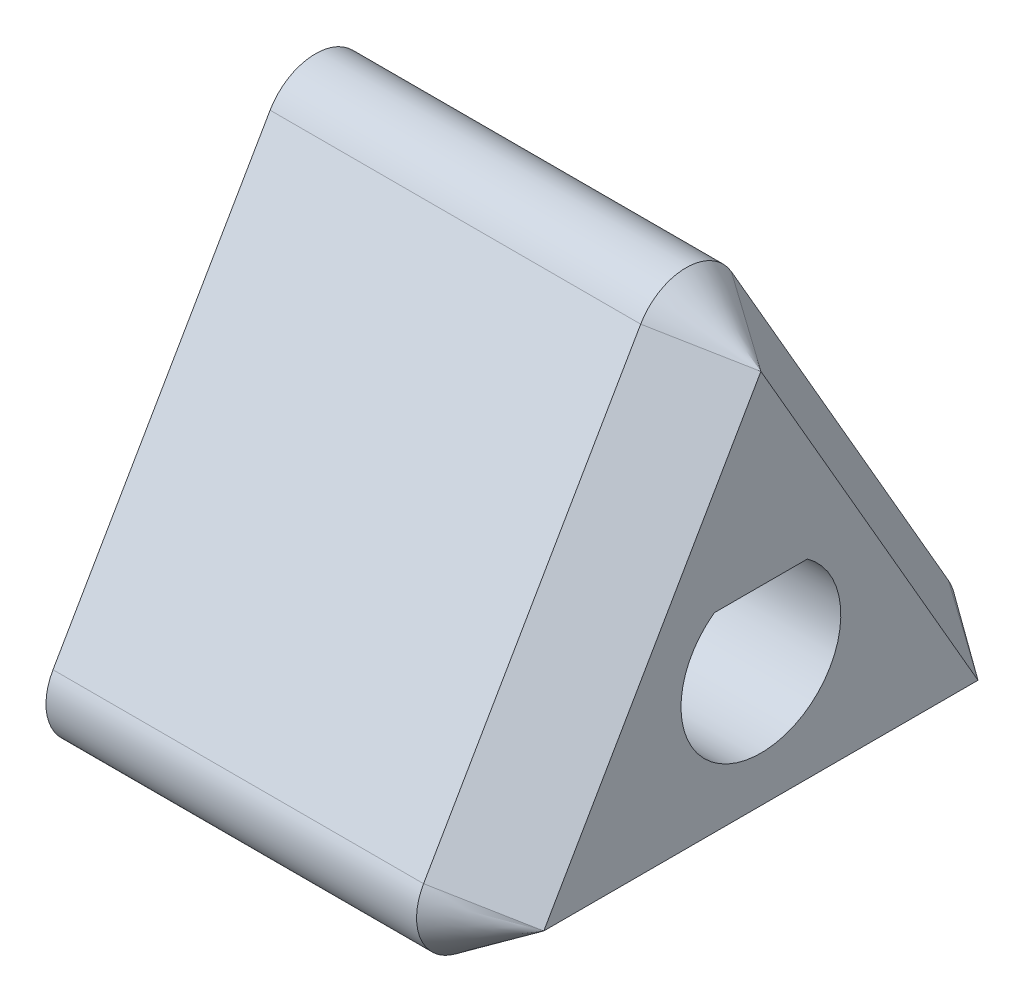
SolidWorks part; units mm, degrees
ref_plane "Ebene vorne" through (0, 0, 0) normal (0, 0, 1) x (1, 0, 0)
ref_plane "Ebene oben" through (0, 0, 0) normal (0, 1, 0) x (1, 0, 0)
ref_plane "Ebene rechts" through (0, 0, 0) normal (1, 0, 0) x (0, 0, -1)
sketch "Skizze1" plane through (0, 0, 0) normal (1, 0, 0) x (0, 0, -1)
  line L1 (0, 13.5677) -> (-11.75, -6.7839)
  line L2 (-11.75, -6.7839) -> (11.75, -6.7839)
  line L3 (11.75, -6.7839) -> (0, 13.5677)
  circle A0 centre (0, 0) radius 6.7839 construction
  dimension "D1" = 23.5
extrude "Aufsatz-Linear austragen1" add sketch "Skizze1" along normal blind 17
sketch "Skizze2" plane through (17, 0, 0) normal (1, 0, 0) x (0, 0, -1)
  line L7 (1.7754, 2.48) -> (-1.7754, 2.48)
  arc A2 (-1.7754, 2.48) -> (1.7754, 2.48) centre (0, 0) ccw
  point P0 (0, 0)
  point P1 (0, 0)
  point P11 (0, 0)
  point P12 (0, 0)
  dimension "D3" = 6.1
  dimension "D1" = 2.48
extrude "Schnitt-Linear austragen1" cut sketch "Skizze2" against normal through all
fillet "Verrundung1" radius 2 3 edges at (8.5, -6.7839, -11.75) (8.5, 13.5677, 0) (8.5, -6.7839, 11.75)
chamfer "Fase1" distance 2 angle 55 6 edges at (17, -5.7839, -10.0179) (17, 3.3919, -5.875) (17, -6.7839, 0) (17, 11.5677, 0) (17, -5.7839, 10.0179) (17, 3.3919, 5.875) first distance on face at (17, -0.285, 0)
chamfer "Fase2" distance 0.5 angle 55 rebuild error yes
